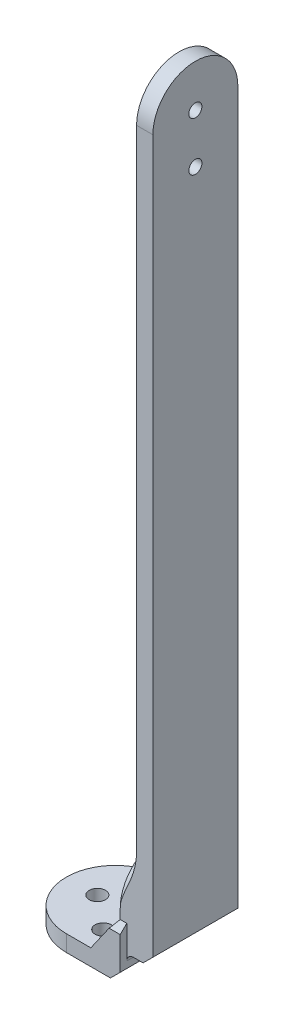
SolidWorks part; units mm, degrees
note: The reader was unsure of these and kept them because the rebuilt part matched: shared geometry of "草图3<2>".
ref_plane "前视基准面" through (0, 0, 0) normal (0, 0, 1) x (1, 0, 0)
ref_plane "上视基准面" through (0, 0, 0) normal (0, 1, 0) x (1, 0, 0)
ref_plane "右视基准面" through (0, 0, 0) normal (1, 0, 0) x (0, 0, -1)
other "Configuration Table"
sketch "草图1" plane through (0, 0, 0) normal (0, 1, 0) x (1, 0, 0)
  line L1 (-19.25, -22) -> (19.25, -22)
  line L2 (-19.25, -22) -> (-19.25, 22)
  line L3 (-19.25, 22) -> (19.25, 22)
  line L4 (19.25, -22) -> (19.25, 22)
  line L5 (-19.25, -22) -> (19.25, 22) construction
  line L6 (-19.25, 22) -> (19.25, -22) construction
  line L7 (0, 0) -> (27.4116, 0) construction
  point P0 (0, 0)
  dimension "D1" = 44
  dimension "D2" = 38.5
extrude "凸台-拉伸1" add sketch "草图1" along normal blind 5
sketch "草图2" plane through (-19.25, 0, 0) normal (-1, 0, 0) x (0, 0, 1)
  line L4 (-22, 0) -> (22, 0)
  line L5 (22, 0) -> (22, 5)
  line L6 (22, 5) -> (-22, 5)
  line L7 (-22, 5) -> (-22, 0)
  line L8 (-22, 0) -> (22, 0)
  line L9 (22, 0) -> (22, 5)
  line L10 (22, 5) -> (-22, 5)
  line L11 (-22, 5) -> (-22, 0)
  dimension "D1" = 0
extrude "凸台-拉伸2" add sketch "草图2" along normal blind 1
sketch "草图3" plane through (-20.25, 0, 0) normal (-1, 0, 0) x (0, 0, 1)
  line L0 (22, 5) -> (-22, 5) construction
  circle A0 centre (0, 5) radius 10
  circle A1 centre (0, 5) radius 13
  line M3 (-22, 0) -> (22, 0)
  line M5 (22, 5) -> (-22, 5)
  dimension "D1" = 20
  dimension "D2" = 26
extrude "凸台-拉伸3" add sketch "草图3" along normal blind 10
extrude "凸台-拉伸4" add sketch "草图3<2>" along normal blind 3 contours A0 M5 | A0 M5 M3 | A0 M3
sketch "草图3<2>" plane through (-20.25, 0, 0) normal (-1, 0, 0) x (0, 0, 1) same geometry as "草图3"
ref_plane "基准面1" through (0, 2.5, 0) normal (0, -1, 0) x (-1, 0, 0)
sketch "草图4" plane through (0, 2.5, 0) normal (0, -1, 0) x (-1, 0, 0)
  line L0 (20.25, 22) -> (25.25, 13)
  line L1 (30.25, 13) -> (20.25, 13) construction
sketch "草图5" plane through (-20.25, 0, 0) normal (1, 0, 0) x (0, 0, -1)
  line L0 (0, 0) -> (0, 97.6749) construction
  line L1 (13, 215) -> (13, 5)
  line L5 (-13, 215) -> (-13, 5)
  arc A0 (-12, 0) -> (12, 0) centre (0, 5) ccw construction
  arc A1 (-12, 0) -> (12, 0) centre (0, 5) ccw
  arc A2 (13, 215) -> (-13, 215) centre (0, 215) ccw
  circle A3 centre (0, 215) radius 2
  circle A4 centre (0, 200) radius 2
  arc A6 (12, 0) -> (13, 5) centre (0, 5) ccw construction
  arc A7 (-13, 5) -> (-12, 0) centre (0, 5) ccw construction
  arc A8 (12, 0) -> (13, 5) centre (0, 5) ccw
  arc A9 (-13, 5) -> (-12, 0) centre (0, 5) ccw
  dimension "D2" = 4
  dimension "D1" = 210
  dimension "D3" = 15
extrude "凸台-拉伸5" add sketch "草图5" against normal blind 5
fillet "圆角1" radius 10 1 edges at (-25.25, 18, 0)
sketch "草图7" plane through (0, 5, 0) normal (0, 1, 0) x (1, 0, 0)
  line L0 (0, 0) -> (13.3446, 0) construction
  line L1 (-9.75, 0) -> (0.2968, -8.25) construction
  line L2 (19.25, -22) -> (19.25, 22) construction
  circle A0 centre (0.2968, -8.25) radius 2.5
  circle A1 centre (-9.75, 0) radius 2.5
  circle A2 centre (0.2968, 8.25) radius 2.5
  dimension "D4" = 5
  dimension "D1" = 13
  dimension "D2" = 16.5
  dimension "D3" = 29
extrude "切除-拉伸1" cut sketch "草图7" against normal up to next
sketch "草图8" plane through (0, 5, 0) normal (0, 1, 0) x (1, 0, 0)
  line L1 (20.25, 22) -> (-20.25, 22)
  line L2 (20.25, 22) -> (20.25, -22)
  line L3 (20.25, -22) -> (-20.25, -22)
  line L4 (-20.25, 22) -> (-20.25, -22)
  line L5 (20.25, 22) -> (-20.25, -22) construction
  line L6 (20.25, -22) -> (-20.25, 22) construction
  point P0 (0, 0)
extrude "切除-拉伸2" cut sketch "草图8" against normal through all
ref_plane "基准面2" through (0, -8, 0) normal (0, -1, 0) x (-1, 0, 0)
sketch "草图9" plane through (0, -8, 0) normal (0, -1, 0) x (-1, 0, 0)
  line L0 (0, 0) -> (40, 0) construction
  line L2 (59.75, -15) -> (20.25, -15)
  line L3 (59.75, -15) -> (59.75, 15)
  line L4 (59.75, 15) -> (20.25, 15)
  line L5 (20.25, -15) -> (20.25, 15)
  line L6 (59.75, -15) -> (20.25, 15) construction
  line L7 (59.75, 15) -> (20.25, -15) construction
  dimension "D1" = 39.5
  dimension "D2" = 30
extrude "凸台-拉伸6" add sketch "草图9" along normal blind 5 separate body
sketch "草图10" plane through (0, -8, 0) normal (0, -1, 0) x (-1, 0, 0)
  line L4 (20.25, -13) -> (30.25, -13)
  line L5 (30.25, -13) -> (30.25, 13)
  line L6 (20.25, -13) -> (30.25, -13)
  line L7 (20.25, 13) -> (20.25, -13)
  line L9 (30.25, -13) -> (30.25, 13)
  line L11 (20.25, 13) -> (20.25, -13)
  line L12 (30.25, 13) -> (20.25, 13)
  line L13 (30.25, 13) -> (20.25, 13)
  dimension "D1" = 0
extrude "凸台-拉伸7" add sketch "草图10" against normal up to surface (13 mm away)
sketch "草图11" plane through (0, -8, 0) normal (0, 1, 0) x (1, 0, 0)
  line L0 (-50.25, 0) -> (-40.2032, 8.25) construction
  line L1 (-50.25, 0) -> (0, 0) construction
  line L2 (-20.25, -13) -> (-20.25, 13) construction
  circle A0 centre (-40.2032, 8.25) radius 2.5
  circle A1 centre (-50.25, 0) radius 2.5
  circle A2 centre (-40.2032, -8.25) radius 2.5
  dimension "D4" = 5
  dimension "D1" = 13
  dimension "D2" = 16.5
  dimension "D3" = 30
extrude "切除-拉伸3" cut sketch "草图11" against normal through all
fillet "圆角2" radius 15 2 edges at (-59.75, -10.5, 15) (-59.75, -10.5, -15)
sketch "草图12" plane through (0, 0, -15) normal (0, 0, -1) x (-1, 0, 0)
  line L2 (28.25, -6) -> (20.25, -6)
  line L3 (28.25, -6) -> (28.25, -13)
  line L4 (28.25, -13) -> (20.25, -13)
  line L5 (20.25, -6) -> (20.25, -13)
  line L6 (28.25, -6) -> (20.25, -13) construction
  line L7 (28.25, -13) -> (20.25, -6) construction
  point P2 (24.25, -9.5)
  dimension "D1" = 7
  dimension "D2" = 8
extrude "切除-拉伸7" cut sketch "草图12" against normal through all
fillet "圆角3" radius 2 1 edges at (-28.25, -6, 0)
sketch "草图13" plane through (-30.25, 0, 0) normal (-1, 0, 0) x (0, 0, 1)
  line L0 (13, -8) -> (-13, -8) construction
  line L1 (-13, -10) -> (13, -10)
  line L2 (-13, -10) -> (-13, -6)
  line L3 (-13, -6) -> (13, -6)
  line L4 (13, -10) -> (13, -6)
  line L5 (-13, -10) -> (13, -6) construction
  line L6 (-13, -6) -> (13, -10) construction
  line L7 (13, 5) -> (13, -8) construction
  point P0 (0, -8)
  dimension "D1" = 4
extrude "凸台-拉伸8" add sketch "草图13" along normal blind 4
sketch "草图14" plane through (0, 0, -13) normal (0, 0, -1) x (-1, 0, 0)
  line L0 (30.25, 2) -> (37.25, -8)
  line L2 (44.75, -8) -> (28.25, -8) construction
  line L3 (37.25, -8) -> (28.25, -8)
  line L4 (28.25, -8) -> (28.25, 2)
  line L5 (28.25, 2) -> (30.25, 2)
  line L6 (30.25, 5) -> (30.25, -6) construction
  dimension "D1" = 7
  dimension "D2" = 10
extrude "凸台-拉伸9" add sketch "草图14" along normal blind 2 and the other way blind 2
mirror "镜向1" about plane through (0, 0, 0) normal (0, 0, 1) of "凸台-拉伸9"
chamfer "倒角1" distance 2 angle 45 1 edges at (-29.25, 2, -15)
chamfer "倒角2" distance 2 angle 45 1 edges at (-29.25, 2, 15)
chamfer "倒角3" distance 3 angle 45 2 edges at (-28.25, -13, 0) (-20.25, -6, 0)
